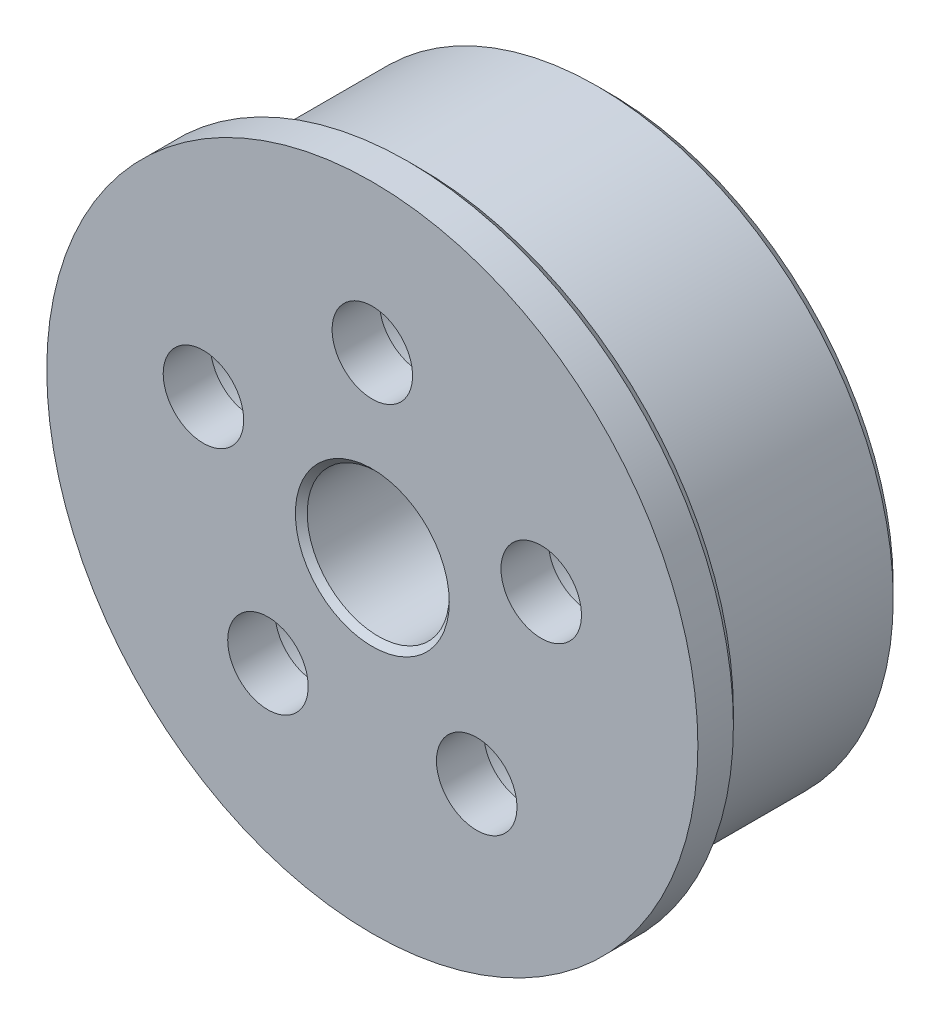
SolidWorks part; units mm, degrees
material "A2017"
ref_plane "正面" through (0, 0, 0) normal (0, 0, 1) x (1, 0, 0)
ref_plane "平面" through (0, 0, 0) normal (0, 1, 0) x (1, 0, 0)
ref_plane "右側面" through (0, 0, 0) normal (1, 0, 0) x (0, 0, -1)
sketch "ｽｹｯﾁ1" plane through (0, 0, 0) normal (0, 0, 1) x (1, 0, 0)
  circle A0 centre (0, 0) radius 12.5
  circle A1 centre (0, 7.5) radius 1.5
  circle A2 centre (0, 0) radius 7.5 construction
  circle A3 centre (7.1329, 2.3176) radius 1.5
  circle A4 centre (4.4084, -6.0676) radius 1.5
  circle A5 centre (-4.4084, -6.0676) radius 1.5
  circle A6 centre (-7.1329, 2.3176) radius 1.5
  point P16 (0, 0)
  dimension "D1" = 25
  dimension "D2" = 15
  dimension "D3" = 3
  dimension "D4" = 5
extrude "ﾎﾞｽ - 押し出し1" add sketch "ｽｹｯﾁ1" along normal blind 10
sketch "ｽｹｯﾁ3" plane through (0, 0, 10) normal (0, 0, 1) x (1, 0, 0)
  circle A0 centre (0, 0) radius 13.75
  circle A2 centre (0, 0) radius 12.5
  circle A3 centre (0, 0) radius 12.5
  dimension "D1" = 0
  dimension "D2" = 27.5
extrude "ﾎﾞｽ - 押し出し3" add sketch "ｽｹｯﾁ3" against normal blind 2
sketch "ｽｹｯﾁ4" plane through (0, 0, 0) normal (0, 0, -1) x (-1, 0, 0)
  circle A0 centre (0, 0) radius 3
  dimension "D1" = 6
extrude "ｶｯﾄ - 押し出し1" cut sketch "ｽｹｯﾁ4" against normal through all
hole_wizard "M3 穴付きねじ用座ぐり穴1" positions "ｽｹｯﾁ5" profile "ｽｹｯﾁ6" counterbore size "M3" standard "JIS" end condition through all
sketch "ｽｹｯﾁ5" plane through (0, 0, 0) normal (0, 0, -1) x (-1, 0, 0)
  point P0 (0, 7.5)
  point P3 (7.1329, 2.3176)
  point P6 (4.4084, -6.0676)
  point P9 (-4.4084, -6.0676)
  point P12 (-7.1329, 2.3176)
sketch "ｽｹｯﾁ6" plane through (0, 7.5, 0) normal (1, 0, 0) x (0, 1, 0)
  line L0 (0, 0) -> (0, 10)
  line L1 (0, 10) -> (1.7, 10)
  line L3 (1.7, 10) -> (1.7, 8)
  line L4 (1.7, 8) -> (3.5, 8)
  line L5 (3.5, 8) -> (3.5, 0)
  line L7 (3.5, 0) -> (0, 0)
  line L11 (0, -6.35) -> (0, 107.95) construction
  dimension "通し穴の直径" = 3.4
  dimension "通し穴の深さ" = 10
  dimension "座ぐり穴の直径" = 7
  dimension "座ぐり穴の深さ" = 8
chamfer "面取り1" distance 0.5 angle 45 2 edges at (12.5, 0, 0) (13.75, 0, 8)
chamfer "面取り2" distance 0.25 angle 45 7 edges at (-3, 0, 0) (-3, 0, 10) (0.9084, -6.0676, 0) (-7.9084, -6.0676, 0) (-10.6329, 2.3176, 0) (-3.5, 7.5, 0) (3.6329, 2.3176, 0)
